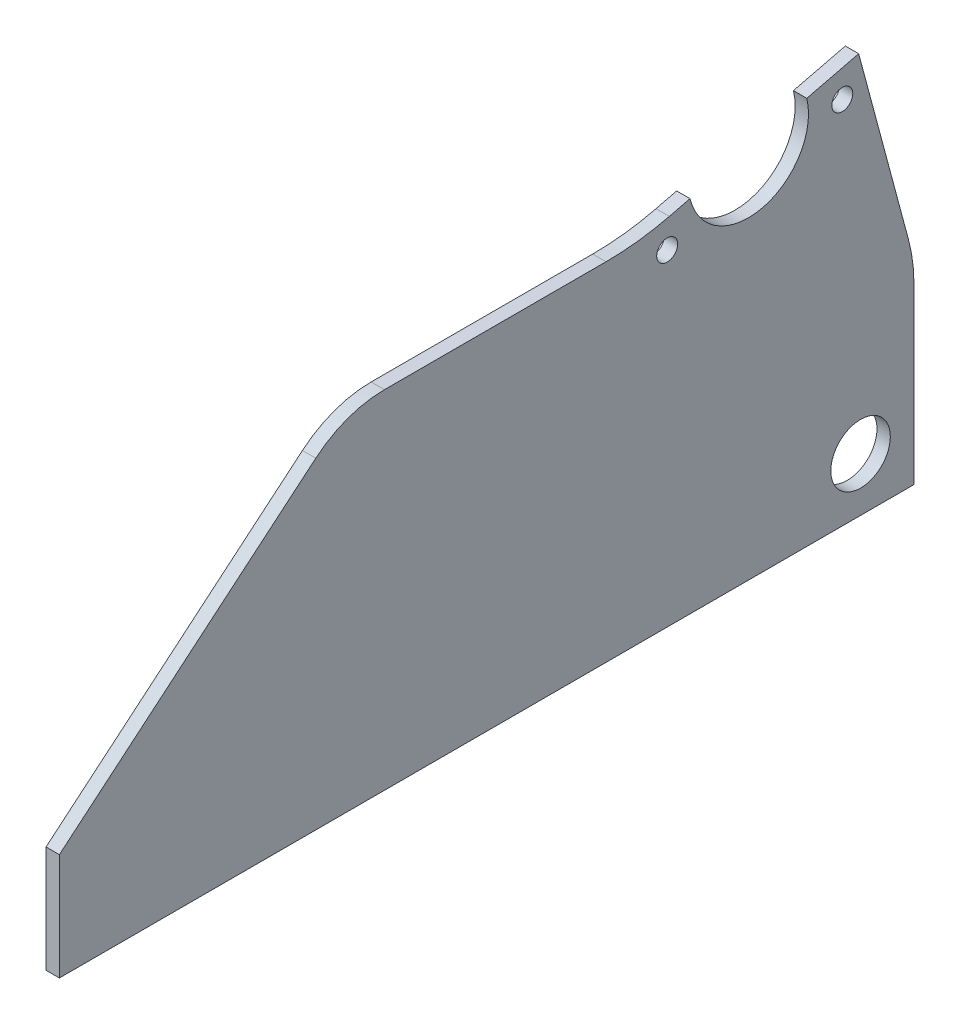
SolidWorks part; units mm, degrees
material "6061-T6 (SS)"
ref_plane "Front Plane" through (0, 0, 0) normal (0, 0, 1) x (1, 0, 0)
ref_plane "Top Plane" through (0, 0, 0) normal (0, 1, 0) x (1, 0, 0)
ref_plane "Right Plane" through (0, 0, 0) normal (1, 0, 0) x (0, 0, -1)
sketch "Sketch1" plane through (0, 0, 0) normal (1, 0, 0) x (0, 0, -1)
  line L0 (0, -25.4) -> (0, 20.8323)
  line L7 (-13.148, 69.9014) -> (-25.4856, 66.889)
  line L8 (-53.2451, 60.111) -> (-65.5826, 57.0986)
  line L10 (-65.5826, 57.0986) -> (-125.9076, 57.0986)
  line L13 (-203.2, -25.4) -> (0, -25.4)
  line L14 (-203.2, -25.4) -> (-203.2, 0)
  line L15 (-203.2, 0) -> (-142.2344, 51.1562)
  line L16 (-203.2, 0) -> (0, 0) construction
  line L17 (-13.148, 69.9014) -> (0, 20.8323)
  arc A2 (-25.4856, 66.889) -> (-53.2451, 60.111) centre (-39.3653, 63.5) cw
  arc A4 (-125.9076, 57.0986) -> (-142.2344, 51.1562) centre (-125.9076, 31.6986) ccw
  circle A5 centre (-39.3653, 63.5) radius 25.4 construction
  point P1 (-15.4429, 74.8803)
  point P4 (0, 0)
  point P7 (-13.5869, 69.4726)
  point P16 (-52.9325, 60.2379)
  dimension "D1" = 28.575
  dimension "D4" = 25.4
  dimension "D7" = 25.4
  dimension "D10" = 50.8
  dimension "D3" = 38.1
  dimension "D2" = 15
  dimension "D5" = 12.7
  dimension "D6" = 203.2
  dimension "D8" = 50
  dimension "D9" = 60.325
  dimension "D11" = 95.3014
extrude "Boss-Extrude1" add sketch "Sketch1" along normal blind 3.175
hole_wizard "#10 Clearance Hole1" positions "Sketch2" profile "Sketch3" hole size "#10" standard "ANSI Inch" end condition through all
sketch "Sketch2" plane through (3.175, 0, 0) normal (1, 0, 0) x (0, 0, -1)
  line L0 (-53.2451, 60.111) -> (-65.5826, 57.0986) construction
  line L1 (-58.6788, 52.2478) -> (-17.0395, 62.4147) construction
  line L3 (-37.8591, 57.3312) -> (-39.3653, 63.5) construction
  line L4 (-13.148, 69.9014) -> (-25.4856, 66.889) construction
  point P0 (-58.6788, 52.2478)
  point P2 (-17.0395, 62.4147)
  dimension "D1" = 42.8625
  dimension "D2" = 6.35
sketch "Sketch3" plane through (3.175, 52.2478, 58.6788) normal (0, 1, 0) x (0, 0, -1)
  line L0 (0, 0) -> (0, 3.175)
  line L1 (0, 3.175) -> (2.4892, 3.175)
  line L2 (2.4892, 3.175) -> (2.4892, 0)
  line L5 (2.4892, 0) -> (0, 0)
  line L11 (0, -6.35) -> (0, 107.95) construction
  dimension "Thru Hole Dia." = 4.9784
  dimension "Thru Hole Depth" = 3.175
sketch "Sketch9" plane through (3.175, 0, 0) normal (1, 0, 0) x (0, 0, -1)
  line L2 (0, -25.4) -> (0, 20.8323) construction
  line L3 (-203.2, -25.4) -> (0, -25.4) construction
  circle A0 centre (-12.7, -12.7) radius 7.0739
  dimension "D1" = 14.1478
  dimension "D3" = 12.7
  dimension "D2" = 12.7
extrude "Cut-Extrude1" cut sketch "Sketch9" against normal through all
fillet "Fillet1" radius 38.1 1 edges at (1.5875, 20.8323, 0)
fillet "Fillet2" radius 63.5 1 edges at (1.5875, 57.0986, 65.5826)
